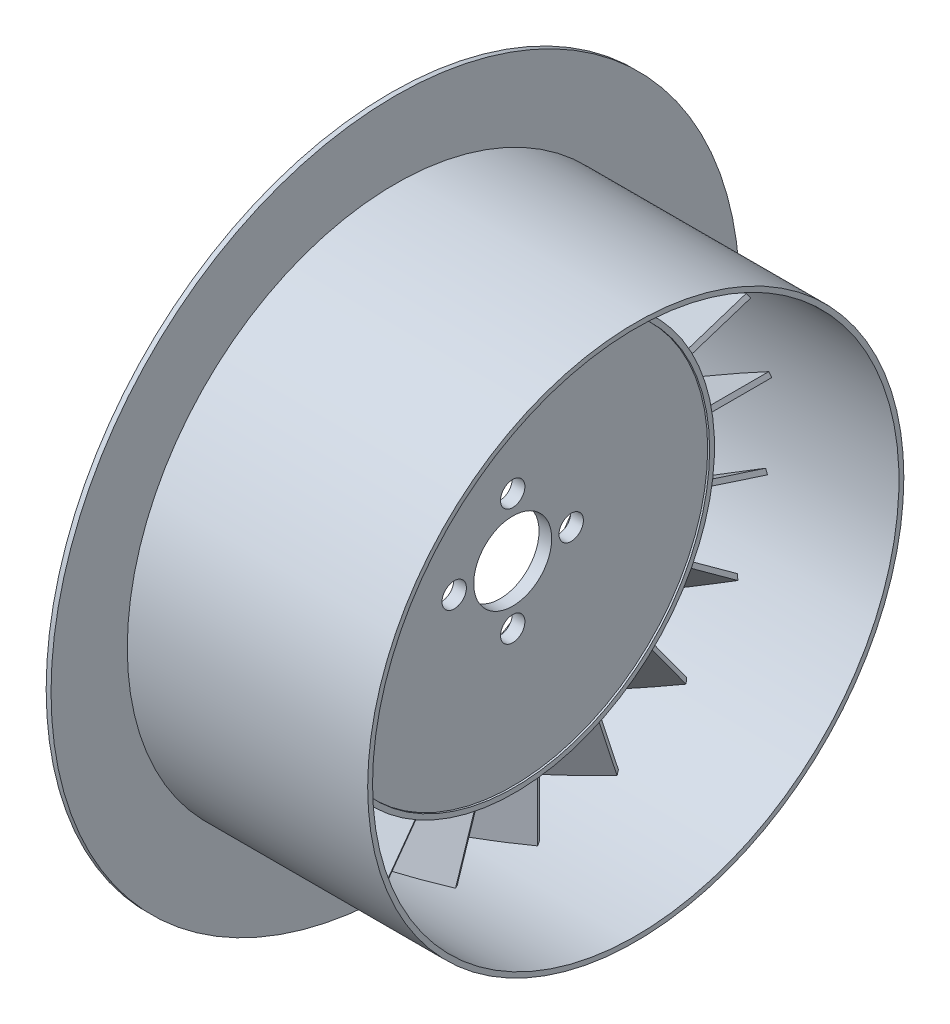
SolidWorks part; units mm, degrees
ref_plane "Front Plane" through (0, 0, 0) normal (0, 0, 1) x (1, 0, 0)
ref_plane "Top Plane" through (0, 0, 0) normal (0, 1, 0) x (1, 0, 0)
ref_plane "Right Plane" through (0, 0, 0) normal (1, 0, 0) x (0, 0, -1)
sketch "Sketch1" plane through (0, 0, 0) normal (0, 1, 0) x (1, 0, 0)
  line L0 (3.302, 0) -> (3.302, 50.8)
  line L1 (3.302, 50.8) -> (3.81, 50.8)
  line L2 (3.81, 50.8) -> (3.81, 52.07)
  line L3 (3.81, 52.07) -> (-25.4, 52.07)
  line L4 (-25.4, 52.07) -> (-25.4, 50.8)
  line L5 (-25.4, 50.8) -> (0, 50.8)
  line L6 (0, 50.8) -> (0, 0)
  line L7 (0, 0) -> (3.302, 0)
  dimension "D1" = 3.302
  dimension "D2" = 1.27
  dimension "D3" = 50.8
  dimension "D4" = 29.21
  dimension "D5" = 25.4
revolve "Revolve1" add sketch "Sketch1" angle 360 about L7
ref_plane "Plane1" through (0, 0, 83.82) normal (0, 0, 1) x (1, 0, 0)
sketch "Sketch2" plane through (0, 0, 83.82) normal (0, 0, 1) x (1, 0, 0)
  line L0 (-24.3107, 7.0701) -> (2.0857, -8.1699)
  line L1 (2.0857, -8.1699) -> (2.7207, -7.0701)
  line L3 (2.7207, -7.0701) -> (-23.6757, 8.1699)
  line L4 (-23.6757, 8.1699) -> (-24.3107, 7.0701)
  line L5 (-25.4, 0) -> (3.81, 0) construction
  line L6 (-25.4, 52.07) -> (-25.4, -52.07) construction
  line L7 (3.81, -52.07) -> (3.81, 52.07) construction
  line L8 (-11.1125, -0.5499) -> (-10.4775, 0.5499) construction
  point P4 (-10.795, 0)
  point P13 (-10.795, 0)
  dimension "D1" = 1.27
  dimension "D2" = 30
  dimension "D3" = 30.48
extrude "Boss-Extrude1" add sketch "Sketch2" along normal blind 16.51 from surface starting at face at (-25.4, 0, 52.07)
pattern_circular "CirPattern15" count 20 over 360 about axis through (3.81, 0, 0) along (-1, 0, 0) of "Boss-Extrude1"
sketch "Sketch7" plane through (3.302, 0, 0) normal (1, 0, 0) x (0, 0, -1)
  circle A0 centre (0, 15.24) radius 3.175
  circle A1 centre (0, 0) radius 10.16
  circle A2 centre (15.24, 0) radius 3.175
  circle A3 centre (0, -15.24) radius 3.175
  circle A4 centre (-15.24, 0) radius 3.175
  point P14 (0, 0)
  dimension "D1" = 6.35
  dimension "D3" = 20.32
  dimension "D2" = 15.24
  dimension "D4" = 4
extrude "Cut-Extrude1" cut sketch "Sketch7" against normal through all
sketch "Sketch8" plane through (0, 0, 0) normal (0, 0, 1) x (1, 0, 0)
  line L0 (35.3606, 69.85) -> (35.3606, 68.58)
  line L1 (35.3606, 68.58) -> (-28.5393, 68.58)
  line L2 (-28.5393, -76.2) -> (-28.5393, 76.2) construction
  line L3 (-28.5393, 68.58) -> (-28.5393, 89.7168)
  line L5 (-28.5393, 89.7168) -> (-27.2693, 89.7168)
  line L6 (-27.2693, 89.7168) -> (-27.2693, 69.85)
  line L7 (-27.2693, 69.85) -> (35.3606, 69.85)
  line L8 (35.3606, -69.85) -> (35.3606, 69.85) construction
  line L9 (-93.6879, 0) -> (-7.1026, 0) construction
  line L10 (0, 0) -> (79.505, 0) construction
  dimension "D1" = 68.58
  dimension "D2" = 1.27
  dimension "D3" = 1.27
revolve "Revolve2" add sketch "Sketch8" angle 360 about L10
